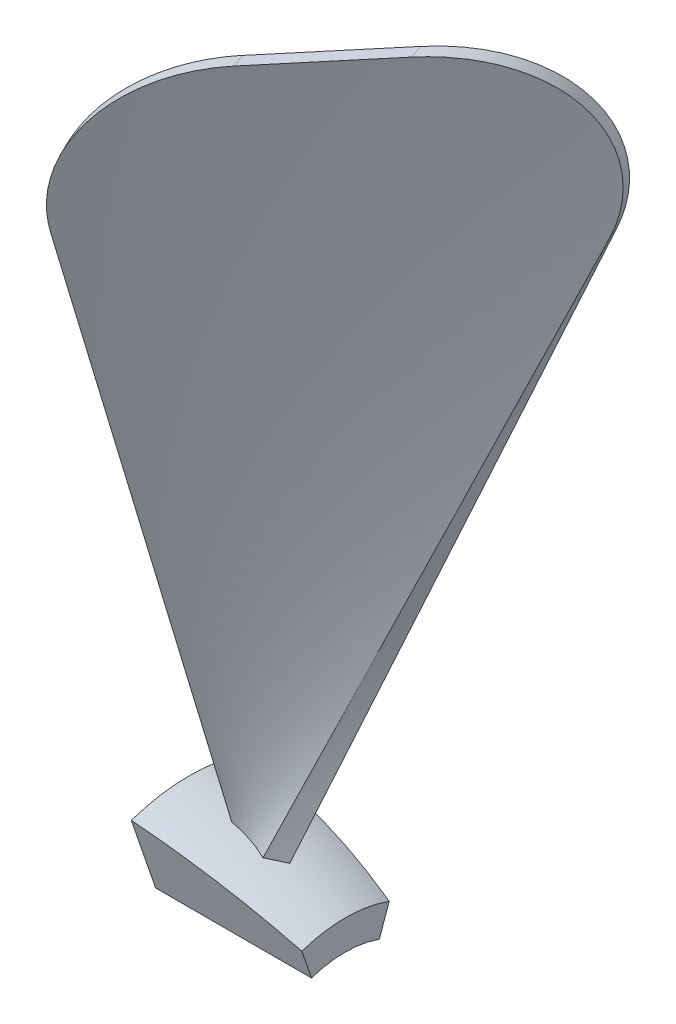
SolidWorks part; units mm, degrees
ref_plane "Спереди" through (0, 0, 0) normal (0, 0, 1) x (1, 0, 0)
ref_plane "Сверху" through (0, 0, 0) normal (0, 1, 0) x (1, 0, 0)
ref_plane "Справа" through (0, 0, 0) normal (1, 0, 0) x (0, 0, -1)
sketch "Эскиз2" plane through (0, 0, 0) normal (0, 0, 1) x (1, 0, 0)
  line L0 (0, 0) -> (0, 28.5)
  line L1 (0, 0) -> (28.5, 0)
  line L2 (-1000, 0) -> (49000, 0) construction
  line L3 (28.5, 0) -> (52.3107, 0)
  spline S0 degree 2 poles (0, 28.5) (31.309, 24.448) (52.3107, 0) knots 0 0 0 1 1 1
revolve "Повернуть1" add sketch "Эскиз2" angle 360 about L2
sketch "Эскиз3" plane through (0, 0, 0) normal (0, 1, 0) x (1, 0, 0)
  line L0 (-1000, 0) -> (49000, 0) construction
  line L1 (16.1294, 0.1091) -> (-47734.5616, -14827.9559) construction
  line L3 (-5.6255, -4.5523) -> (-47756.3165, -14832.6173) construction
  line L4 (14.9853, 1.848) -> (15.5785, -0.062)
  line L5 (15.5785, -0.062) -> (16.9582, 0.3664)
  line L6 (16.9582, 0.3664) -> (16.3651, 2.2764)
  line L7 (16.3651, 2.2764) -> (14.9853, 1.848)
ref_plane "Плоскость4" through (0, 0, 0) normal (0, -1, 0) x (-1, 0, 0)
ref_plane "Плоскость5" through (0, 140, 0) normal (0, -1, 0) x (-1, 0, 0)
sketch "Эскиз5" plane through (0, 140, 0) normal (0, 1, 0) x (1, 0, 0)
  line L0 (-134.2963, -185.9376) -> (-32273.6768, -38488.1597) construction
  line L1 (-137.3753, -192.7185) -> (-32276.7557, -38494.9407) construction
  line L2 (-1.9101, -28.1658) -> (-0.3779, -29.4515)
  line L3 (-0.3779, -29.4515) -> (52.0513, 33.0312)
  line L4 (52.0513, 33.0312) -> (50.5191, 34.3169)
  line L5 (50.5191, 34.3169) -> (-1.9101, -28.1658)
ref_plane "Плоскость6" through (0, 10, 0) normal (0, -1, 0) x (-1, 0, 0)
ref_plane "Плоскость7" through (0, 20, 0) normal (0, -1, 0) x (-1, 0, 0)
sketch "Эскиз6" plane through (0, 20, 0) normal (0, -1, 0) x (-1, 0, 0)
  line L0 (-1028.3504, 0.2589) -> (48971.6496, 0.2589) construction
  line L1 (-14.611, -2.0966) -> (-38316.8331, 32137.2839) construction
  line L2 (-28.0566, 16.3522) -> (-38330.2788, 32155.7327) construction
  line L3 (-11.5241, 2.4797) -> (-15.0529, -1.7258)
  line L4 (-15.0529, -1.7258) -> (-12.3899, -3.9603)
  line L5 (-12.3899, -3.9603) -> (-8.8611, 0.2452)
  line L6 (-8.8611, 0.2452) -> (-11.5241, 2.4797)
loft "По сечениям6" add profiles "Эскиз5", "Эскиз6" connector at (52.0513, 140, -33.0312) connector at (12.3899, 20, 3.9603)
fillet "Скругление3" radius 20 2 edges
sketch "Эскиз7" plane through (0, 0, 0) normal (-1, 0, 0) x (0, 0, 1)
  circle A0 centre (0, 0) radius 12.6
extrude "Вырез-Вытянуть1" cut sketch "Эскиз7" against normal blind 10
sketch "Эскиз8" plane through (0, 0, 0) normal (-1, 0, 0) x (0, 0, 1)
  circle A0 centre (0, 0) radius 16.5
extrude "Вырез-Вытянуть2" cut sketch "Эскиз8" against normal blind 2
sketch "Эскиз9" plane through (0, 0, 0) normal (-1, 0, 0) x (0, 0, 1)
  line L0 (0, 0) -> (-226.0396, 49979.4656) construction
  line L1 (-8.438, 140) -> (7.1716, 140) construction
  line L2 (0, 0) -> (16263.3452, 47281.1125) construction
  line L3 (0, 0) -> (-16690.343, 47132.0746) construction
  line L4 (-5.5078, 15.5536) -> (-10.6921, 30.1934)
  line L5 (5.3669, 15.6028) -> (10.3854, 30.1927)
  circle A0 centre (0, 0) radius 16.5 construction
  arc A1 (-5.5078, 15.5536) -> (5.3669, 15.6028) centre (0, 0) cw
  arc A2 (-10.6921, 30.1934) -> (10.3854, 30.1927) centre (-0.1544, -0.0698) ccw
  point P5 (-0.6332, 140)
extrude "Вырез-Вытянуть3" cut sketch "Эскиз9" against normal blind 25
sketch "Эскиз10" plane through (25, 0, 0) normal (-1, 0, 0) x (0, 0, 1)
  circle A0 centre (0, 0) radius 21.2536
extrude "Вырез-Вытянуть4" cut sketch "Эскиз10" against normal blind 40
